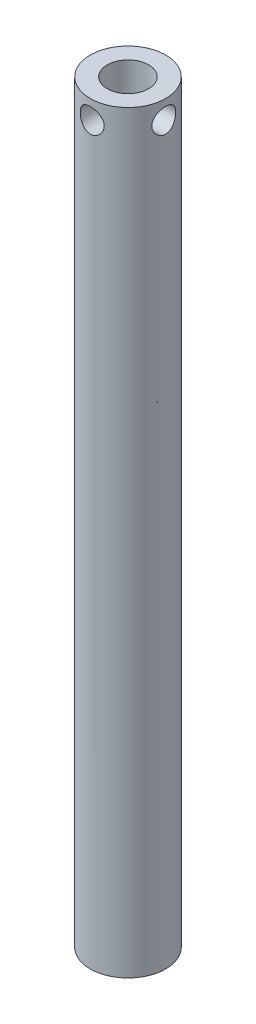
SolidWorks part; units mm, degrees
material "Brass"
ref_plane "Front Plane" through (0, 0, 0) normal (0, 0, 1) x (1, 0, 0)
ref_plane "Top Plane" through (0, 0, 0) normal (0, 1, 0) x (1, 0, 0)
ref_plane "Right Plane" through (0, 0, 0) normal (1, 0, 0) x (0, 0, -1)
sketch "Sketch1" plane through (0, 0, 0) normal (0, 1, 0) x (1, 0, 0)
  circle A0 centre (0, 0) radius 1
  circle A1 centre (0, 0) radius 0.55
  dimension "D1" = 2
  dimension "D2" = 0.45
extrude "Boss-Extrude1" add sketch "Sketch1" along normal blind 20
hole_wizard "#72 (0.025) Diameter Hole1" positions "3DSketch1" profile "Sketch2" hole size "#72" standard "ANSI Inch" end condition up to next
sketch3d "3DSketch1"
  line L0 (0, 20, 0) -> (0, 19.5, 0) construction
  line L3 (0, 19.5, 0) -> (0, 19.5, 1) construction
  line L8 (0, 19.5, 0) -> (1, 19.5, 0) construction
  point P17 (1, 19.5, 0)
  point P19 (0, 19.5, 1)
  dimension "D1" = 0.5
sketch "Sketch2" plane through (1, 19.5, 0) normal (0, 1, 0) x (0, 0, -1)
  line L0 (0, 0) -> (0, 0.45)
  line L1 (0, 0.45) -> (0.3175, 0.45)
  line L2 (0.3175, 0.45) -> (0.3175, 0)
  line L5 (0.3175, 0) -> (0, 0)
  line L11 (0, -6.35) -> (0, 107.95) construction
  dimension "Thru Hole Dia." = 0.635
  dimension "Thru Hole Depth" = 0.45
hole_wizard "#54 (0.055) Diameter Hole1" positions "Sketch4" profile "Sketch3" hole size "#54" standard "ANSI Inch"
sketch "Sketch4" plane through (0, 0, 0) normal (0, -1, 0) x (-1, 0, 0)
  point P0 (0, 0)
sketch "Sketch3" plane through (0, 0, 0) normal (1, 0, 0) x (0, 0, -1)
  line L0 (0, 0) -> (0, 4.4197)
  line L1 (0, 4.4197) -> (0.6985, 4)
  line L2 (0.6985, 4) -> (0.6985, 0)
  line L5 (0.6985, 0) -> (0, 0)
  line L10 (0, 4.4197) -> (-0.6985, 4) construction
  line L11 (0, -6.35) -> (0, 107.95) construction
  dimension "Hole Dia." = 1.397
  dimension "Hole Depth" = 4
  dimension "Drill Angle" = 118
